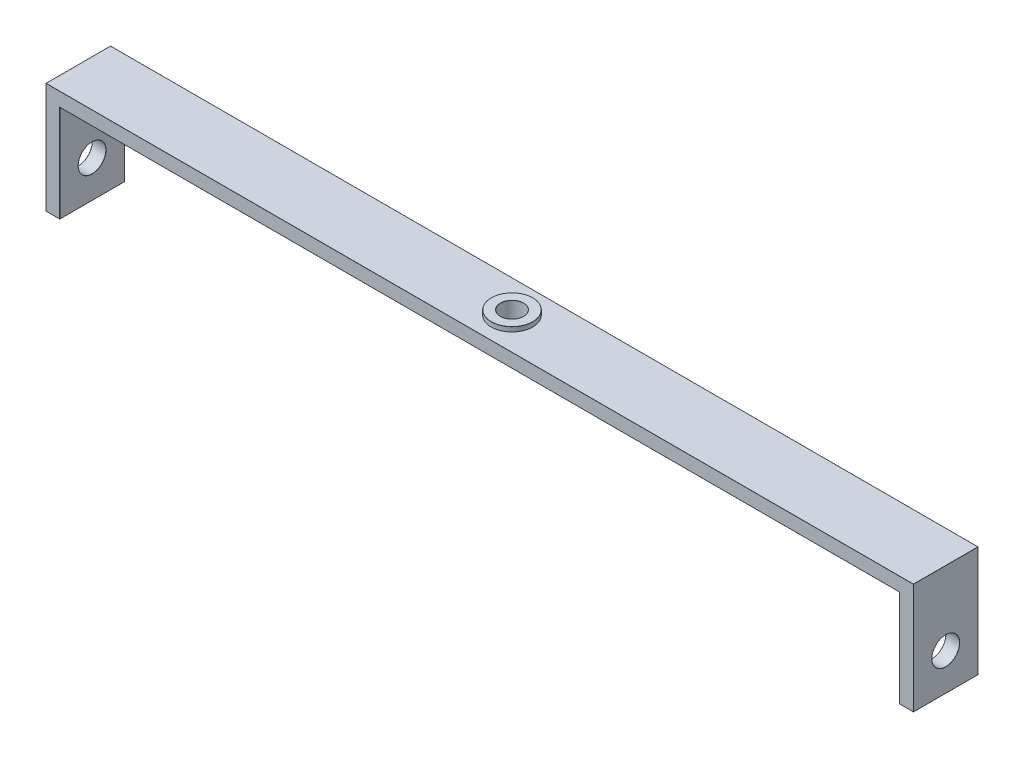
SolidWorks part; units mm, degrees
ref_plane "Front Plane" through (0, 0, 0) normal (0, 0, 1) x (1, 0, 0)
ref_plane "Top Plane" through (0, 0, 0) normal (0, 1, 0) x (1, 0, 0)
ref_plane "Right Plane" through (0, 0, 0) normal (1, 0, 0) x (0, 0, -1)
sketch "Sketch1" plane through (0, 0, 0) normal (0, 0, 1) x (1, 0, 0)
  line L0 (-62.6214, 18.8137) -> (-62.6214, 30.8137)
  line L1 (-62.6214, 30.8137) -> (31.3786, 30.8137)
  line L2 (31.3786, 30.8137) -> (31.3786, 18.8137)
  line L3 (-61.1214, 18.8137) -> (-61.1214, 29.3137)
  line L4 (-61.1214, 29.3137) -> (29.8786, 29.3137)
  line L5 (29.8786, 29.3137) -> (29.8786, 18.8137)
  line L6 (-62.6214, 18.8137) -> (-61.1214, 18.8137)
  line L7 (29.8786, 18.8137) -> (31.3786, 18.8137)
  dimension "D1" = 94
  dimension "D2" = 12
  dimension "D3" = 1.5
extrude "Boss-Extrude1" add sketch "Sketch1" along normal blind 3.5 and the other way blind 3.5
sketch "Sketch3" plane through (0, 30.8137, 0) normal (0, 1, 0) x (1, 0, 0)
  circle A0 centre (-15.6214, 0) radius 1.25
  dimension "D1" = 2.5
extrude "Cut-Extrude5" cut sketch "Sketch3" against normal blind 3.5
sketch "Sketch5" plane through (0, 30.8137, 0) normal (0, 1, 0) x (1, 0, 0)
  circle A1 centre (-15.6214, 0) radius 1.25 construction
  circle A2 centre (-15.6214, 0) radius 2.25
  circle A3 centre (-15.6214, 0) radius 2.25
  circle A4 centre (-15.6214, 0) radius 1.25
  dimension "D1" = 1
extrude "Boss-Extrude2" add sketch "Sketch5" along normal blind 0.5
sketch "Sketch6" plane through (0, 0, 0) normal (1, 0, 0) x (0, 0, -1)
  line L0 (0, 31.3137) -> (0, 18.8137) construction
  line L1 (2.25, 31.3137) -> (-2.25, 31.3137) construction
  line L2 (3.5, 18.8137) -> (-3.5, 18.8137) construction
  circle A0 centre (0, 22.8137) radius 1.5
  dimension "D1" = 3
  dimension "D2" = 8.5
extrude "Cut-Extrude6" cut sketch "Sketch6" along normal up to surface and the other way up to surface up to face at (31.3786, 24.8137, 0) other way up to face at (-62.6214, 24.8137, 0)
fillet "Fillet1" radius 0.01 29 edges at (-15.6214, 29.3137, -3.5) (31.3786, 24.3137, 0) (31.3786, 24.8137, -3.5) (31.3786, 18.8137, 0) (31.3786, 24.8137, 3.5) (31.3786, 30.8137, 0) (-61.1214, 24.0637, -3.5) (-61.1214, 18.8137, 0) (-61.1214, 24.0637, 3.5) (-61.1214, 29.3137, 0) (-62.6214, 24.8137, -3.5) (-62.6214, 30.8137, 0) (-62.6214, 24.8137, 3.5) (-62.6214, 18.8137, 0) (-16.8714, 31.3137, 0) (-17.8714, 31.3137, 0) (29.8786, 24.0637, -3.5) (29.8786, 18.8137, 0) (29.8786, 22.8137, 1.5) (29.8786, 24.0637, 3.5) (-61.8714, 18.8137, 3.5) (-15.6214, 29.3137, 3.5) (-15.6214, 30.8137, -3.5) (-15.6214, 30.8137, 3.5) (-61.1214, 22.8137, -1.5) (-61.8714, 18.8137, -3.5) (-62.6214, 22.8137, 1.5) (30.6286, 18.8137, -3.5) (30.6286, 18.8137, 3.5)
